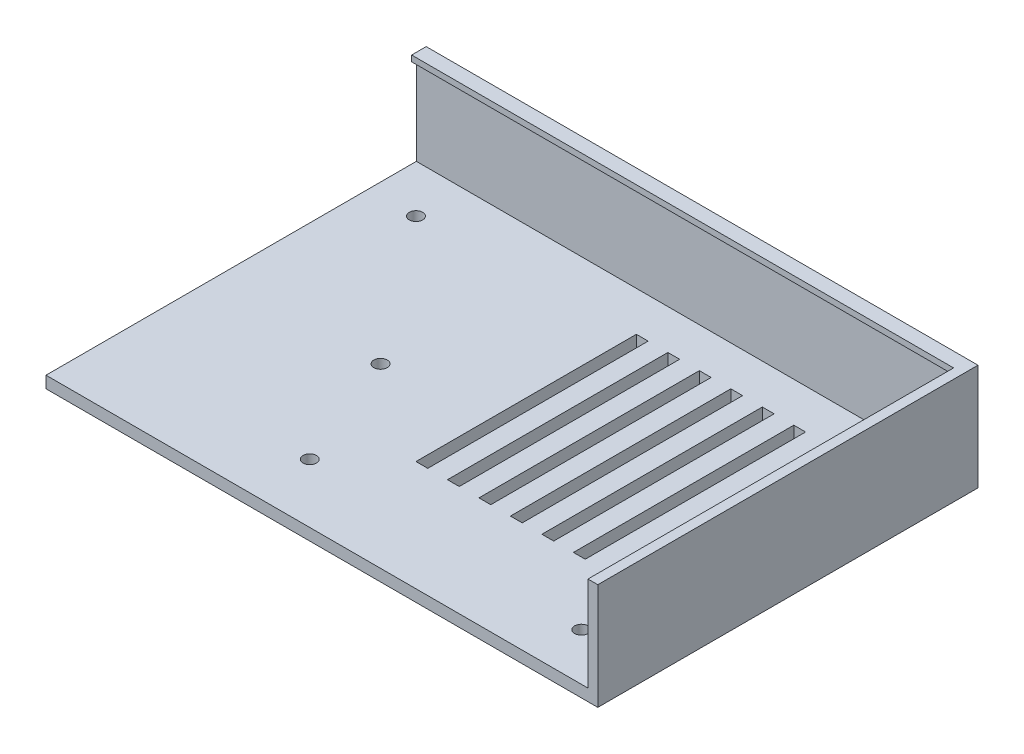
SolidWorks part; units mm, degrees
ref_plane "Front Plane" through (0, 0, 0) normal (0, 0, 1) x (1, 0, 0)
ref_plane "Top Plane" through (0, 0, 0) normal (0, 1, 0) x (1, 0, 0)
ref_plane "Right Plane" through (0, 0, 0) normal (1, 0, 0) x (0, 0, -1)
sketch "Sketch1" plane through (0, 0, 0) normal (0, 1, 0) x (1, 0, 0)
  line L1 (-140.2, -96.6) -> (140.2, -96.6)
  line L2 (-140.2, -96.6) -> (-140.2, 96.6)
  line L3 (-140.2, 96.6) -> (140.2, 96.6)
  line L4 (140.2, -96.6) -> (140.2, 96.6)
  line L5 (-140.2, -96.6) -> (140.2, 96.6) construction
  line L6 (-140.2, 96.6) -> (140.2, -96.6) construction
  point P0 (0, 0)
  dimension "D1" = 280.4
  dimension "D2" = 193.2
extrude "Shell Block" add sketch "Sketch1" along normal blind 27
ref_plane "Shell Front" through (0, 27, 0) normal (0, 1, 0) x (1, 0, 0)
sketch "Sketch2" plane through (0, 27, 0) normal (0, 1, 0) x (1, 0, 0)
  line L1 (-137.7, -92.9) -> (137.7, -92.9)
  line L2 (-137.7, -92.9) -> (-137.7, 92.9)
  line L3 (-137.7, 92.9) -> (137.7, 92.9)
  line L4 (137.7, -92.9) -> (137.7, 92.9)
  line L5 (-137.7, -92.9) -> (137.7, 92.9) construction
  line L6 (-137.7, 92.9) -> (137.7, -92.9) construction
  point P0 (0, 0)
  dimension "D1" = 275.4
  dimension "D2" = 185.8
extrude "Front Opening" cut sketch "Sketch2" against normal blind 1.5
ref_plane "Under Lip" through (0, 25.5, 0) normal (0, 1, 0) x (1, 0, 0)
sketch "Sketch3" plane through (0, 25.5, 0) normal (0, 1, 0) x (1, 0, 0)
  line L1 (-137.7, -94.1) -> (137.7, -94.1)
  line L2 (-137.7, -94.1) -> (-137.7, 94.1)
  line L3 (-137.7, 94.1) -> (137.7, 94.1)
  line L4 (137.7, -94.1) -> (137.7, 94.1)
  line L5 (-137.7, -94.1) -> (137.7, 94.1) construction
  line L6 (-137.7, 94.1) -> (137.7, -94.1) construction
  point P0 (0, 0)
  dimension "D1" = 275.4
  dimension "D2" = 188.2
extrude "Display Pocket" cut sketch "Sketch3" against normal blind 22.5
ref_plane "Back Inner" through (0, 3, 0) normal (0, 1, 0) x (1, 0, 0)
sketch "Sketch4" plane through (0, 3, 0) normal (0, 1, 0) x (1, 0, 0)
  line L1 (66, 28) -> (69, 28)
  line L2 (66, 28) -> (66, 84)
  line L3 (66, 84) -> (69, 84)
  line L4 (69, 28) -> (69, 84)
  line L6 (66, -84) -> (69, -84)
  line L7 (66, -84) -> (66, -28)
  line L8 (66, -28) -> (69, -28)
  line L9 (69, -84) -> (69, -28)
  line L11 (74, 28) -> (77, 28)
  line L12 (74, 28) -> (74, 84)
  line L13 (74, 84) -> (77, 84)
  line L14 (77, 28) -> (77, 84)
  line L16 (74, -84) -> (77, -84)
  line L17 (74, -84) -> (74, -28)
  line L18 (74, -28) -> (77, -28)
  line L19 (77, -84) -> (77, -28)
  line L21 (82, 28) -> (85, 28)
  line L22 (82, 28) -> (82, 84)
  line L23 (82, 84) -> (85, 84)
  line L24 (85, 28) -> (85, 84)
  line L26 (82, -84) -> (85, -84)
  line L27 (82, -84) -> (82, -28)
  line L28 (82, -28) -> (85, -28)
  line L29 (85, -84) -> (85, -28)
  line L31 (90, 28) -> (93, 28)
  line L32 (90, 28) -> (90, 84)
  line L33 (90, 84) -> (93, 84)
  line L34 (93, 28) -> (93, 84)
  line L36 (90, -84) -> (93, -84)
  line L37 (90, -84) -> (90, -28)
  line L38 (90, -28) -> (93, -28)
  line L39 (93, -84) -> (93, -28)
  line L41 (98, 28) -> (101, 28)
  line L42 (98, 28) -> (98, 84)
  line L43 (98, 84) -> (101, 84)
  line L44 (101, 28) -> (101, 84)
  line L46 (98, -84) -> (101, -84)
  line L47 (98, -84) -> (98, -28)
  line L48 (98, -28) -> (101, -28)
  line L49 (101, -84) -> (101, -28)
  line L51 (106, 28) -> (109, 28)
  line L52 (106, 28) -> (106, 84)
  line L53 (106, 84) -> (109, 84)
  line L54 (109, 28) -> (109, 84)
  line L56 (106, -84) -> (109, -84)
  line L57 (106, -84) -> (106, -28)
  line L58 (106, -28) -> (109, -28)
  line L59 (109, -84) -> (109, -28)
  line L61 (114, 28) -> (117, 28)
  line L62 (114, 28) -> (114, 84)
  line L63 (114, 84) -> (117, 84)
  line L64 (117, 28) -> (117, 84)
  line L66 (114, -84) -> (117, -84)
  line L67 (114, -84) -> (114, -28)
  line L68 (114, -28) -> (117, -28)
  line L69 (117, -84) -> (117, -28)
  line L71 (122, 28) -> (125, 28)
  line L72 (122, 28) -> (122, 84)
  line L73 (122, 84) -> (125, 84)
  line L74 (125, 28) -> (125, 84)
  line L76 (122, -84) -> (125, -84)
  line L77 (122, -84) -> (122, -28)
  line L78 (122, -28) -> (125, -28)
  line L79 (125, -84) -> (125, -28)
extrude "Vent Slots" cut sketch "Sketch4" against normal blind 4
sketch "Sketch5" plane through (0, 0, 0) normal (1, 0, 0) x (0, 0, -1)
  line L1 (-35, 5) -> (35, 5)
  line L2 (-35, 5) -> (-35, 21)
  line L3 (-35, 21) -> (35, 21)
  line L4 (35, 5) -> (35, 21)
extrude "Cable Exit (+X short side)" cut sketch "Sketch5" against normal blind 141.2
sketch "Sketch6" plane through (0, 3, 0) normal (0, 1, 0) x (1, 0, 0)
  circle A0 centre (-40, -45) radius 1.7
  circle A1 centre (-40, 45) radius 1.7
  circle A2 centre (40, -45) radius 1.7
  circle A3 centre (40, 45) radius 1.7
  circle A4 centre (-52, -15) radius 1.7
  circle A5 centre (-52, 15) radius 1.7
  circle A6 centre (52, -15) radius 1.7
  circle A7 centre (52, 15) radius 1.7
  circle A8 centre (-12, -82) radius 1.7
  circle A9 centre (-12, 82) radius 1.7
  circle A10 centre (12, -82) radius 1.7
  circle A11 centre (12, 82) radius 1.7
  circle A12 centre (-124, -12) radius 1.7
  circle A13 centre (-124, 12) radius 1.7
  circle A14 centre (124, -12) radius 1.7
  circle A15 centre (124, 12) radius 1.7
extrude "Bolt Holes" cut sketch "Sketch6" against normal blind 4
sketch "Sketch7" plane through (0, 0, 0) normal (0, 1, 0) x (1, 0, 0)
  line L1 (-200, -200) -> (0, -200)
  line L2 (-200, -200) -> (-200, 200)
  line L3 (-200, 200) -> (0, 200)
  line L4 (0, -200) -> (0, 200)
extrude "Keep one half (X)" cut sketch "Sketch7" against normal through all and the other way through all
sketch "Sketch8" plane through (0, 0, 0) normal (0, 1, 0) x (1, 0, 0)
  line L1 (-200, 0) -> (200, 0)
  line L2 (-200, 0) -> (-200, -200)
  line L3 (-200, -200) -> (200, -200)
  line L4 (200, 0) -> (200, -200)
extrude "Keep one quarter (Z)" cut sketch "Sketch8" against normal through all and the other way through all
equation "\"DispL\"= 274.2"
equation "\"DispW\"= 187.0"
equation "\"DispT\"= 20.0"
equation "\"Clr\"= 0.6"
equation "\"Wall\"= 2.5"
equation "\"BackT\"= 3.0"
equation "\"CableRoom\"= 4.0"
equation "\"LipW\"= 1.2"
equation "\"LipT\"= 1.5"
equation "\"CableW\"= 70.0"
equation "\"CableH\"= 16.0"
equation "\"BoltD\"= 3.4"
equation "\"ShellL\"= \"DispL\" + 2 * \"Clr\" + 2 * \"Wall\""
equation "\"ShellW\"= \"DispW\" + 2 * \"Clr\" + 2 * \"Wall\""
equation "\"ShellH\"= \"BackT\" + \"DispT\" + \"CableRoom\""
equation "\"D1@Sketch1\" = \"ShellL\""
equation "\"D2@Sketch1\" = \"ShellW\""
equation "\"D1@Shell Block\" = \"ShellH\""
equation "\"D1@Shell Front\" = \"ShellH\""
equation "\"D1@Sketch2\" = \"DispL\" + 2 * \"Clr\""
equation "\"D2@Sketch2\" = \"DispW\" + 2 * \"Clr\" - 2 * \"LipW\""
equation "\"D1@Front Opening\" = \"LipT\""
equation "\"D1@Under Lip\" = \"ShellH\" - \"LipT\""
equation "\"D1@Sketch3\" = \"DispL\" + 2 * \"Clr\""
equation "\"D2@Sketch3\" = \"DispW\" + 2 * \"Clr\""
equation "\"D1@Display Pocket\" = \"ShellH\" - \"LipT\" - \"BackT\""
equation "\"D1@Back Inner\" = \"BackT\""
